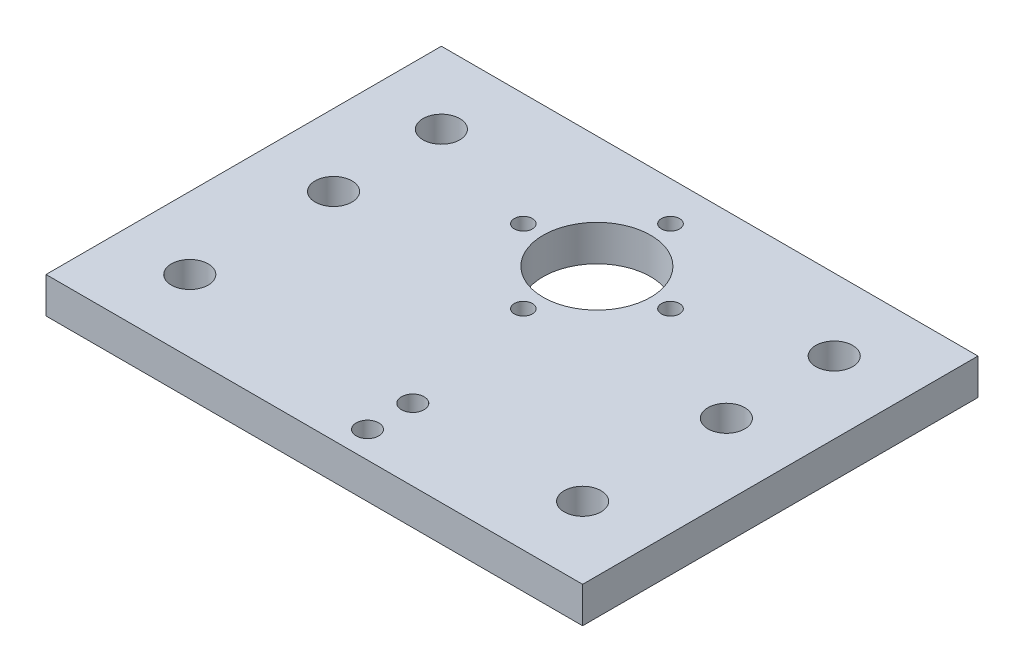
SolidWorks part; units mm, degrees
ref_plane "Front Plane" through (0, 0, 0) normal (0, 0, 1) x (1, 0, 0)
ref_plane "Top Plane" through (0, 0, 0) normal (0, 1, 0) x (1, 0, 0)
ref_plane "Right Plane" through (0, 0, 0) normal (1, 0, 0) x (0, 0, -1)
sketch "Sketch1" plane through (0, 0, 0) normal (0, 1, 0) x (1, 0, 0)
  line L0 (-34.7, 3.175) -> (34.7, 3.175) construction
  line L1 (-47.4, 34.925) -> (47.4, 34.925)
  line L2 (-47.4, 34.925) -> (-47.4, -34.925)
  line L3 (-47.4, -34.925) -> (47.4, -34.925)
  line L4 (47.4, 34.925) -> (47.4, -34.925)
  line L5 (-47.4, 34.925) -> (47.4, -34.925) construction
  line L6 (-47.4, -34.925) -> (47.4, 34.925) construction
  line L7 (22, -34.925) -> (47.4, -34.925) construction
  line L8 (4.7, -30.225) -> (4.7, -22.225) construction
  line L9 (-34.7, -22.225) -> (34.7, -22.225) construction
  line L10 (-34.7, -22.225) -> (-34.7, 22.225) construction
  line L11 (-34.7, 22.225) -> (34.7, 22.225) construction
  line L12 (34.7, -22.225) -> (34.7, 22.225) construction
  line L13 (-34.7, -22.225) -> (34.7, 22.225) construction
  line L14 (-34.7, 22.225) -> (34.7, -22.225) construction
  line L15 (0, 0) -> (0, 15) construction
  line L16 (4.7, -30.225) -> (18.2, -30.225) construction
  line L17 (22, -34.925) -> (22, -9.525) construction
  line L18 (22, -9.525) -> (47.4, -9.525) construction
  line L19 (47.4, -34.925) -> (47.4, -9.525) construction
  line L20 (22, -34.925) -> (47.4, -9.525) construction
  line L21 (22, -9.525) -> (47.4, -34.925) construction
  circle A18 centre (-34.7, 22.225) radius 3.2576
  circle A19 centre (34.7, 22.225) radius 3.2576
  circle A20 centre (34.7, -22.225) radius 3.2576
  circle A21 centre (-34.7, -22.225) radius 3.2576
  circle A22 centre (4.7, -30.225) radius 2
  circle A23 centre (4.7, -22.225) radius 2
  circle A24 centre (0, 15) radius 9.5
  circle A25 centre (0, 15) radius 13 construction
  circle A26 centre (0, 28) radius 1.5 construction
  circle A27 centre (-13, 15) radius 1.5 construction
  circle A28 centre (13, 15) radius 1.5 construction
  circle A29 centre (0, 2) radius 1.5 construction
  circle A30 centre (-34.7, 3.175) radius 3.2576
  circle A31 centre (34.7, 3.175) radius 3.2576
  dimension "D2" = 30
  dimension "D4" = 19
  dimension "D7" = 26
  dimension "D13" = 12.7
  dimension "D15" = 6.5151
  dimension "D16" = 8
  dimension "D17" = 4
  dimension "D9" = 3
  dimension "D5" = 15
  dimension "D6" = 94.8
  dimension "D8" = 69.85
  dimension "D11" = 25.4
  dimension "D14" = 12.7
  dimension "D3" = 13.5
extrude "Boss-Extrude1" add sketch "Sketch1" along normal blind 6.35
hole_wizard "CSK for M3 Flat Head Machine Screw1" positions "Sketch7" profile "Sketch8" countersink size "M3" standard "ANSI Metric" end condition through all
sketch "Sketch7" plane through (0, 0, 0) normal (0, -1, 0) x (-1, 0, 0)
  point P0 (-13, 15)
  point P3 (0, 2)
  point P6 (13, 15)
  point P9 (0, 28)
sketch "Sketch8" plane through (13, 0, -15) normal (1, 0, 0) x (0, 0, -1)
  line L0 (0, 0) -> (0, 6.35)
  line L1 (0, 6.35) -> (1.6, 6.35)
  line L2 (1.6, 6.35) -> (1.6, 1.55)
  line L3 (1.6, 1.55) -> (3.15, 0)
  line L5 (3.15, 0) -> (0, 0)
  line L6 (-1.6, 1.55) -> (-3.15, 0) construction
  line L11 (0, -6.35) -> (0, 107.95) construction
  dimension "Thru Hole Dia." = 3.2
  dimension "Thru Hole Depth" = 6.35
  dimension "Near C'Sink Dia." = 6.3
  dimension "Near C'Sink Angle" = 90
equation "\"testbed_height\" = 91.50mm"
equation "\"plate_thickness\" = 6mm"
equation "\"main_body_splay_length\" = 48.5mm"
equation "\"splay_shaft_length_no_wires\" = 10mm"
equation "\"splay_shaft_length_wires\" = 6.5mm"
equation "\"timing_pulley_offset\" = 0mm"
equation "\"effective_motor_length\" = \"timing_pulley_offset\" + \"splay_shaft_length_no_wires\" + \"main_body_splay_length\""
equation "\"80_20_side\" = 25.4mm"
equation "\"80_20_length\" = 152.4mm"
equation "\"80_20_optic_mount_length\" = \"80_20_length\" - 25.4mm"
equation "\"optic_board_hole_size\" = 6.35mm"
equation "\"total_mounting_length\" = \"testbed_height\" - \"effective_motor_length\" - \"80_20_side\""
equation "\"mounting_vertical_portion_height\" = \"total_mounting_length\" - 2 * \"plate_thickness\""
equation "\"face_mount_width\" = 15.25mm"
equation "\"center_dist_to_face_mount_vertical_screws\" = 5mm"
equation "\"D1@Boss-Extrude1\"=0.25in"
